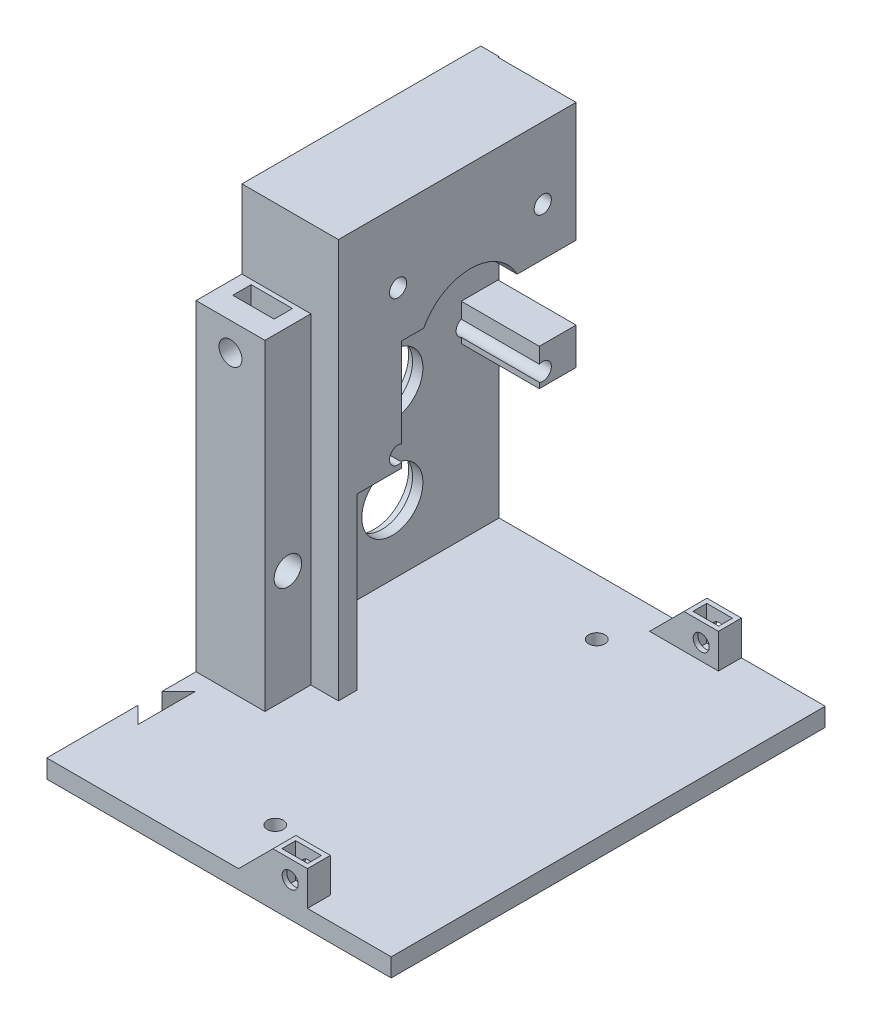
SolidWorks part; units mm, degrees
ref_plane "Front Plane" through (0, 0, 0) normal (0, 0, 1) x (1, 0, 0)
ref_plane "Top Plane" through (0, 0, 0) normal (0, 1, 0) x (1, 0, 0)
ref_plane "Right Plane" through (0, 0, 0) normal (1, 0, 0) x (0, 0, -1)
sketch "Sketch20" plane through (0, 0, 0) normal (0, 1, 0) x (1, 0, 0)
  line L1 (75, 0) -> (0, 0)
  line L2 (75, 0) -> (75, -94.5)
  line L3 (75, -94.5) -> (0, -94.5)
  line L4 (0, 0) -> (0, -94.5)
  dimension "D1" = 94.5
  dimension "D2" = 75
extrude "Base" add sketch "Sketch20" along normal blind 4 separate body
sketch "Sketch21" plane through (0, 4, 0) normal (0, 1, 0) x (1, 0, 0)
  line L0 (0, 0) -> (0, -94.5) construction
  line L1 (0, -52) -> (21, -52)
  line L2 (0, -52) -> (0, -48)
  line L3 (0, -48) -> (21, -48)
  line L4 (21, -52) -> (21, -48)
  line L6 (75, 0) -> (0, 0) construction
  dimension "D1" = 4
  dimension "D2" = 48
  dimension "D3" = 21
extrude "X_Wall" add sketch "Sketch21" along normal blind 87
sketch "Sketch22" plane through (0, 4, 0) normal (0, 1, 0) x (1, 0, 0)
  line L0 (75, 0) -> (0, 0) construction
  line L1 (0, -48) -> (4, -48)
  line L2 (0, -48) -> (0, 0)
  line L3 (0, 0) -> (4, 0)
  line L4 (4, -48) -> (4, 0)
  dimension "D1" = 4
extrude "Y_Wall" add sketch "Sketch22" along normal blind 87
sketch "Sketch23" plane through (0, 4, 0) normal (0, 1, 0) x (1, 0, 0)
  line L1 (0, -52) -> (15, -52)
  line L2 (0, -52) -> (0, -62)
  line L3 (0, -62) -> (15, -62)
  line L4 (15, -52) -> (15, -62)
  dimension "D1" = 15
  dimension "D2" = 10
extrude "Belt_Screw_Mount" add sketch "Sketch23" along normal blind 70
sketch "Sketch24" plane through (4, 0, 0) normal (1, 0, 0) x (0, 0, -1)
  line L0 (-48, 41) -> (-48, 91)
  line L1 (-48, 91) -> (-0.25, 91)
  line L2 (-0.25, 91) -> (-0.25, 41) construction
  line L3 (-0.25, 41) -> (-8.25, 41)
  line L4 (-8.25, 41) -> (-8.25, 65) construction
  line L5 (-8.25, 65) -> (-38.25, 65)
  line L6 (-38.25, 65) -> (-38.25, 41)
  line L7 (-38.25, 41) -> (-48, 41)
  line L8 (-48, 91) -> (0, 91) construction
  line L11 (-48, 91) -> (-48, 4) construction
  line L13 (-8.25, 41) -> (-8.25, 49)
  line L14 (-0.25, 41) -> (-0.25, 49)
  line L16 (-0.25, 49) -> (-8.25, 49)
  line L17 (-8.25, 65) -> (-0.25, 65)
  line L18 (-0.25, 91) -> (-0.25, 65)
  point P10 (-23.25, 65)
  dimension "D1" = 30
  dimension "D2" = 24
  dimension "D3" = 26
  dimension "D4" = 8
  dimension "D5" = 24.75
  dimension "D6" = 8
extrude "Motor_Spacer" add sketch "Sketch24" along normal blind 17
sketch "Sketch14" plane through (0, 0, 0) normal (-1, 0, 0) x (0, 0, 1)
  line L0 (23.25, 40.65) -> (23.25, 19) construction
  line L2 (23.25, 40.65) -> (23.25, 59.65) construction
  line L3 (7.5, 43.9) -> (39, 43.9) construction
  line L4 (7.5, 43.9) -> (39, 75.4) construction
  line L5 (39, 43.9) -> (7.5, 75.4) construction
  line L6 (7.5, 75.4) -> (39, 75.4) construction
  line L8 (0, 0) -> (94.5, 0) construction
  line L9 (52, 91) -> (52, 74) construction
  circle A0 centre (23.25, 19) radius 6.65
  circle A1 centre (23.25, 40.65) radius 6.65
  circle A2 centre (23.25, 59.65) radius 3.75
  circle A3 centre (39, 75.4) radius 1.875
  circle A4 centre (39, 43.9) radius 1.875
  circle A5 centre (7.5, 43.9) radius 1.875
  circle A6 centre (7.5, 75.4) radius 1.875
  point P18 (23.25, 59.65)
  dimension "D1" = 21.65
  dimension "D2" = 13.3
  dimension "D3" = 13.3
  dimension "D6" = 7.5
  dimension "D7" = 3.75
  dimension "D8" = 3.75
  dimension "D9" = 3.75
  dimension "D10" = 3.75
  dimension "D4" = 19
  dimension "D5" = 19
  dimension "D11" = 31.5
  dimension "D12" = 31.5
  dimension "D13" = 31.5
  dimension "D14" = 31.5
  dimension "D15" = 13
extrude "Motor_Bearing_Holes" cut sketch "Sketch14" against normal blind 21
sketch "Sketch15" plane through (0, 0, 0) normal (-1, 0, 0) x (0, 0, 1)
  circle A0 centre (23.25, 19) radius 7.55
  circle A1 centre (23.25, 40.65) radius 7.55
  circle A4 centre (23.25, 40.65) radius 6.65 construction
  circle A5 centre (23.25, 19) radius 6.65 construction
  dimension "D1" = 15.1
  dimension "D2" = 15.1
extrude "Bearing_Holes_2" cut sketch "Sketch15" against normal blind 1.75
sketch "Sketch17" plane through (0, 0, 62) normal (0, 0, 1) x (1, 0, 0)
  line L3 (7.5, 74) -> (7.5, 67.9) construction
  line L4 (0, 74) -> (15, 74) construction
  circle A0 centre (7.5, 67.9) radius 2.5
  dimension "D1" = 5
  dimension "D2" = 6.1
extrude "Belt_Screw_Hole" cut sketch "Sketch17" against normal blind 8
sketch "Sketch18" plane through (0, 74, 0) normal (0, 1, 0) x (1, 0, 0)
  line L0 (0, -57) -> (15, -57) construction
  line L1 (3, -53) -> (12, -53)
  line L2 (3, -53) -> (3, -57)
  line L3 (3, -57) -> (12, -57)
  line L4 (12, -53) -> (12, -57)
  line L10 (0, -52) -> (0, -62) construction
  line L11 (15, -62) -> (15, -52) construction
  point P7 (7.5, -57)
  point P11 (7.5, -57)
  point P13 (7.5, -57)
  dimension "D1" = 4
  dimension "D2" = 9
extrude "Belt_Bolt_Hole" cut sketch "Sketch18" against normal blind 10.35
sketch "Sketch25" plane through (21, 0, 0) normal (1, 0, 0) x (0, 0, -1)
  circle A0 centre (-23.25, 59.65) radius 11.5
  dimension "D1" = 23
extrude "Motor_Cutout" cut sketch "Sketch25" against normal blind 17
sketch "Sketch26" plane through (0, 0, 0) normal (-1, 0, 0) x (0, 0, 1)
  line L0 (52, 74) -> (52, 0) construction
  line L1 (0, 0) -> (94.5, 0) construction
  line L4 (57, 28) -> (52, 28)
  line L6 (57, 28) -> (57, 0) construction
  circle A0 centre (57, 28) radius 1.75
  dimension "D1" = 5
  dimension "D2" = 28
extrude "Connector_Screw-hole" cut sketch "Sketch26" against normal blind 15 contours A0 region at (0, 26.2995, 57)
sketch "Sketch42" plane through (15, 0, 0) normal (1, 0, 0) x (0, 0, -1)
  circle A0 centre (-57, 28) radius 3
  dimension "D1" = 6
extrude "Cut-Extrude2" cut sketch "Sketch42" against normal blind 7
sketch "Sketch27" plane through (0, 0, 0) normal (0, -1, 0) x (1, 0, 0)
  line L0 (0, 47.25) -> (75, 47.25) construction
  line L1 (0, 0) -> (0, 94.5) construction
  line L2 (75, 94.5) -> (75, 0) construction
  line L3 (0, 47.25) -> (0, 72) construction
  line L4 (0, 69.5) -> (0, 74.5) construction
  line L8 (0, 74.5) -> (3.5355, 78.0355) construction
  line L9 (3.5355, 78.0355) -> (3.5355, 65.9645) construction
  line L10 (3.5355, 65.9645) -> (0, 69.5) construction
  line L15 (3.6355, 65.723) -> (-0.1, 69.4586)
  line L16 (-0.1, 69.4586) -> (-0.1, 74.5414)
  line L17 (-0.1, 74.5414) -> (3.6355, 78.277)
  line L18 (3.6355, 78.277) -> (3.6355, 65.723)
  line L19 (3.6355, 16.223) -> (3.6355, 28.777)
  line L20 (-0.1, 19.9586) -> (3.6355, 16.223)
  line L21 (-0.1, 25.0414) -> (-0.1, 19.9586)
  line L22 (3.6355, 28.777) -> (-0.1, 25.0414)
  point P10 (0, 72)
  dimension "D1" = 20
  dimension "D2" = 5
  dimension "D3" = 5
  dimension "D4" = 5
  dimension "D5" = 45
  dimension "D6" = 0.1
extrude "DoveTailCutout" cut sketch "Sketch27" against normal blind 4.2
sketch "Sketch28" plane through (0, 0, 94.5) normal (0, 0, 1) x (1, 0, 0)
  line L0 (56.75, 4) -> (56.75, 11.5)
  line L1 (56.75, 11.5) -> (49.25, 11.5)
  line L2 (49.25, 11.5) -> (41.75, 4)
  line L3 (41.75, 4) -> (56.75, 4)
  line L4 (75, 4) -> (75, 0) construction
  line L6 (0, 4) -> (75, 4) construction
  dimension "D1" = 7.5
  dimension "D2" = 7.5
  dimension "D3" = 45
  dimension "D4" = 18.25
extrude "Front_Right_Case_Screw_Body" add sketch "Sketch28" against normal blind 5
sketch "Sketch29" plane through (0, 0, 94.5) normal (0, 0, 1) x (1, 0, 0)
  line L0 (56.75, 4) -> (56.75, 11.5) construction
  line L4 (0, 0) -> (75, 0) construction
  circle A0 centre (53, 7.5) radius 1.75
  dimension "D1" = 3.5
  dimension "D2" = 3.75
  dimension "D3" = 7.5
extrude "Front_Right_Case_Screw_Hole" cut sketch "Sketch29" against normal blind 10
sketch "Sketch30" plane through (0, 11.5, 0) normal (0, 1, 0) x (1, 0, 0)
  line L0 (56.75, -94.5) -> (49.25, -94.5) construction
  line L1 (50.2, -90.5) -> (55.8, -90.5)
  line L2 (50.2, -90.5) -> (50.2, -93.5)
  line L3 (50.2, -93.5) -> (55.8, -93.5)
  line L4 (55.8, -90.5) -> (55.8, -93.5)
  line L5 (56.75, -89.5) -> (56.75, -94.5) construction
  point P6 (53, -93.5)
  dimension "D1" = 3
  dimension "D2" = 5.6
  dimension "D3" = 1
  dimension "D4" = 3.75
extrude "Front_Right_Case_Nut_Hole" cut sketch "Sketch30" against normal blind 7.5
ref_plane "Right_Front_Case_Screw_Plane" through (0, 0, 80.75) normal (0, 0, 1) x (1, 0, 0)
sketch "Sketch31" plane through (0, 0, 80.75) normal (0, 0, 1) x (1, 0, 0)
  line L0 (75, 4) -> (75, 11.5)
  line L1 (75, 11.5) -> (70, 11.5)
  line L2 (70, 11.5) -> (62.5, 4)
  line L3 (62.5, 4) -> (75, 4)
  line L5 (0, 4) -> (41.75, 4) construction
  line L6 (75, 4) -> (75, 0) construction
  dimension "D1" = 5
  dimension "D2" = 7.5
  dimension "D3" = 45
extrude "Right_Front_Case_Screw_Body" [suppressed] add sketch "Sketch31" against normal blind 7.5
sketch "Sketch32" [suppressed] plane through (75, 0, 0) normal (1, 0, 0) x (0, 0, -1)
  line L0 (-73.25, 7.5) -> (-80.75, 7.5) construction
  line L1 (-73.25, 4) -> (-73.25, 11.5) construction
  line L2 (-80.75, 6.325) -> (-80.75, -6.325) construction
  line L3 (-94.5, 0) -> (0, 0) construction
  circle A0 centre (-77, 7.5) radius 1.75
  point P11 (-77, 7.5)
  dimension "D1" = 3.5
  dimension "D2" = 7.5
extrude "Right_Front_Case_Screw_Hole" [suppressed] cut sketch "Sketch32" against normal blind 9
sketch "Sketch33" [suppressed] plane through (0, 11.5, 0) normal (0, 1, 0) x (1, 0, 0)
  line L0 (74, -80.75) -> (74, -73.25) construction
  line L1 (71, -74.2) -> (74, -74.2)
  line L2 (71, -74.2) -> (71, -79.8)
  line L3 (71, -79.8) -> (74, -79.8)
  line L4 (74, -74.2) -> (74, -79.8)
  line L8 (75, -80.75) -> (70, -80.75) construction
  line L9 (75, -73.25) -> (70, -73.25) construction
  line L10 (75, -73.25) -> (75, -80.75) construction
  point P12 (74, -77)
  point P13 (74, -77)
  dimension "D1" = 3
  dimension "D2" = 5.6
  dimension "D3" = 1
extrude "Right_Front_Case_Nut_Hole" [suppressed] cut sketch "Sketch33" against normal blind 7.5
ref_plane "Plane2" through (0, 0, 10.75) normal (0, 0, -1) x (-1, 0, 0)
sketch "Sketch34" plane through (0, 0, 10.75) normal (0, 0, -1) x (-1, 0, 0)
  line L0 (-75, 4) -> (-75, 11.5)
  line L1 (-75, 11.5) -> (-70, 11.5)
  line L2 (-70, 11.5) -> (-62.5, 4)
  line L3 (-62.5, 4) -> (-75, 4)
  line L4 (0, 4) -> (-41.75, 4) construction
  line L5 (-75, 4) -> (-75, 0) construction
  dimension "D1" = 45
  dimension "D2" = 5
  dimension "D3" = 7.5
extrude "Right_Back_Case_Screw_Body" [suppressed] add sketch "Sketch34" against normal blind 7.5
sketch "Sketch35" [suppressed] plane through (75, 0, 0) normal (1, 0, 0) x (0, 0, -1)
  line L0 (-10.75, 7.5) -> (-18.25, 7.5) construction
  line L1 (-10.75, 11.5) -> (-10.75, 4) construction
  line L2 (-18.25, 11.5) -> (-18.25, 4) construction
  line L3 (-94.5, 0) -> (0, 0) construction
  circle A0 centre (-14.5, 7.5) radius 1.75
  point P11 (-14.5, 7.5)
  dimension "D1" = 3.5
  dimension "D2" = 7.5
extrude "Right_Back_Case_Screw_Hole" [suppressed] cut sketch "Sketch35" against normal blind 9
sketch "Sketch36" [suppressed] plane through (0, 11.5, 0) normal (0, 1, 0) x (1, 0, 0)
  line L0 (74, -18.25) -> (74, -10.75) construction
  line L1 (71, -11.7) -> (74, -11.7)
  line L2 (71, -11.7) -> (71, -17.3)
  line L3 (71, -17.3) -> (74, -17.3)
  line L4 (74, -11.7) -> (74, -17.3)
  line L5 (75, -18.25) -> (62.5, -18.25) construction
  line L6 (70, -10.75) -> (75, -10.75) construction
  line L7 (75, -18.25) -> (75, -10.75) construction
  point P12 (74, -14.5)
  point P13 (74, -14.5)
  dimension "D1" = 5.6
  dimension "D2" = 3
  dimension "D3" = 1
extrude "Right_Back_Case_Nut_Hole" [suppressed] cut sketch "Sketch36" against normal blind 7.5
sketch "Sketch37" plane through (0, 0, 0) normal (0, 0, -1) x (-1, 0, 0)
  line L0 (-56.75, 4) -> (-56.75, 11.5)
  line L1 (-21, 4) -> (-4, 4) construction
  line L2 (-56.75, 11.5) -> (-49.25, 11.5)
  line L3 (-49.25, 11.5) -> (-41.75, 4)
  line L4 (-41.75, 4) -> (-56.75, 4)
  line L5 (-75, 4) -> (-75, 0) construction
  dimension "D1" = 7.5
  dimension "D2" = 7.5
  dimension "D3" = 45
  dimension "D4" = 18.25
extrude "Back_Right_Case_Screw_Body" add sketch "Sketch37" against normal blind 5 separate body
sketch "Sketch38" plane through (0, 0, 0) normal (0, 0, -1) x (-1, 0, 0)
  line L5 (-75, 0) -> (0, 0) construction
  line L6 (-56.75, 11.5) -> (-56.75, 4) construction
  circle A0 centre (-53, 7.5) radius 1.75
  dimension "D1" = 3.5
  dimension "D2" = 3.75
  dimension "D3" = 7.5
extrude "Back_Right_Case_Screw_Hole" cut sketch "Sketch38" against normal blind 5
sketch "Sketch39" plane through (0, 11.5, 0) normal (0, 1, 0) x (1, 0, 0)
  line L0 (49.25, -1) -> (56.75, -1) construction
  line L1 (50.2, -1) -> (55.8, -1)
  line L2 (50.2, -1) -> (50.2, -4)
  line L3 (50.2, -4) -> (55.8, -4)
  line L4 (55.8, -1) -> (55.8, -4)
  line L5 (49.25, -5) -> (49.25, 0) construction
  line L6 (56.75, -5) -> (56.75, 0) construction
  line L7 (49.25, 0) -> (56.75, 0) construction
  point P12 (53, -1)
  point P13 (53, -1)
  dimension "D1" = 5.6
  dimension "D2" = 3
  dimension "D3" = 1
extrude "Back_Right_Case_Nut_Hole" cut sketch "Sketch39" against normal blind 7.5
sketch "Sketch40" plane through (0, 0, 0) normal (0, -1, 0) x (1, 0, 0)
  line L0 (37.5, 94.5) -> (37.5, 82.25) construction
  line L1 (0, 94.5) -> (75, 94.5) construction
  line L2 (37.5, 82.25) -> (37.5, 47.25) construction
  line L3 (37.5, 47.25) -> (37.5, 12.25) construction
  line L4 (37.5, 12.25) -> (37.5, 0) construction
  line L5 (75, 0) -> (0, 0) construction
  circle A0 centre (37.5, 82.25) radius 1.75
  circle A1 centre (37.5, 12.25) radius 1.75
  dimension "D1" = 3.5
  dimension "D2" = 3.5
  dimension "D3" = 35
extrude "Foot_Holes" cut sketch "Sketch40" against normal blind 10
sketch "Sketch41" plane through (4, 0, 0) normal (1, 0, 0) x (0, 0, -1)
  line L0 (-44.25, 4) -> (-38.25, 4)
  line L1 (-48, 4) -> (0, 4) construction
  line L2 (-38.25, 4) -> (-38.25, 26)
  line L5 (-44.25, 26) -> (-44.25, 4)
  line L7 (-44.25, 26) -> (-38.25, 26)
  line L8 (-48, 11) -> (-46.125, 11) construction
  line L9 (-48, 41) -> (-48, 4) construction
  line L10 (-46.125, 11) -> (-44.25, 11) construction
  line L11 (-46.125, 11) -> (-46.125, 6) construction
  circle A0 centre (-46.125, 11) radius 1
  circle A1 centre (-46.125, 6) radius 1
  point P4 (-41.25, 4)
  dimension "D3" = 2
  dimension "D5" = 2
  dimension "D1" = 6
  dimension "D2" = 22
  dimension "D4" = 6.75
  dimension "D6" = 2
  dimension "D7" = 5
extrude "Motor_Cable_Passthrough" cut sketch "Sketch41" against normal up to next (4 mm away)
